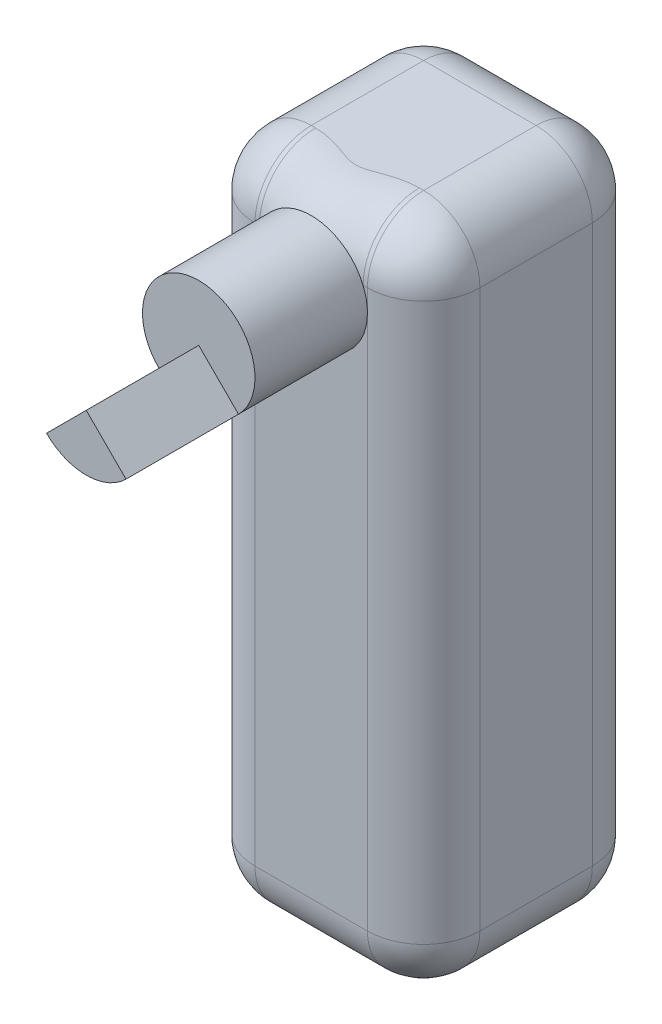
SolidWorks part; units mm, degrees
ref_plane "Front Plane" through (0, 0, 0) normal (0, 0, 1) x (1, 0, 0)
ref_plane "Top Plane" through (0, 0, 0) normal (0, 1, 0) x (1, 0, 0)
ref_plane "Right Plane" through (0, 0, 0) normal (1, 0, 0) x (0, 0, -1)
sketch "Sketch1" plane through (0, 0, 0) normal (0, 0, 1) x (1, 0, 0)
  line L0 (-5, -12.265) -> (5, -12.265)
  line L2 (-5, -12.265) -> (-5, 17.5)
  line L3 (-5, 17.5) -> (5, 17.5)
  line L4 (5, -12.265) -> (5, 17.5)
  line L5 (-3.5043, -12.265) -> (5, 17.5) construction
  line L6 (-5, 17.5) -> (3.5043, -12.265) construction
  point P0 (0, 0)
extrude "Boss-Extrude1" add sketch "Sketch1" along normal blind 10
sketch "Sketch2" plane through (0, 0, 10) normal (0, 0, 1) x (1, 0, 0)
  circle A0 centre (0, 14.0348) radius 2.5
extrude "Boss-Extrude2" add sketch "Sketch2" along normal blind 5
fillet "Fillet1" radius 2.5 12 edges at (0, 17.5, 0) (-5, 2.6175, 0) (0, -12.265, 0) (5, 2.6175, 0) (0, -12.265, 10) (5, -12.265, 5) (-5, -12.265, 5) (5, 2.6175, 10) (5, 17.5, 5) (0, 17.5, 10) (-5, 2.6175, 10) (-5, 17.5, 5)
sketch "Sketch3" plane through (0, 0, 15) normal (0, 0, 1) x (1, 0, 0)
  line L3 (-1.7678, 12.267) -> (0, 14.0348)
  line L4 (1.7678, 12.267) -> (0, 14.0348)
  arc A0 (-1.7678, 12.267) -> (0, 11.5348) centre (0, 14.0348) ccw
  arc A1 (0, 11.5348) -> (1.7678, 12.267) centre (0, 14.0348) ccw
extrude "Boss-Extrude4" add sketch "Sketch3" along normal blind 5
